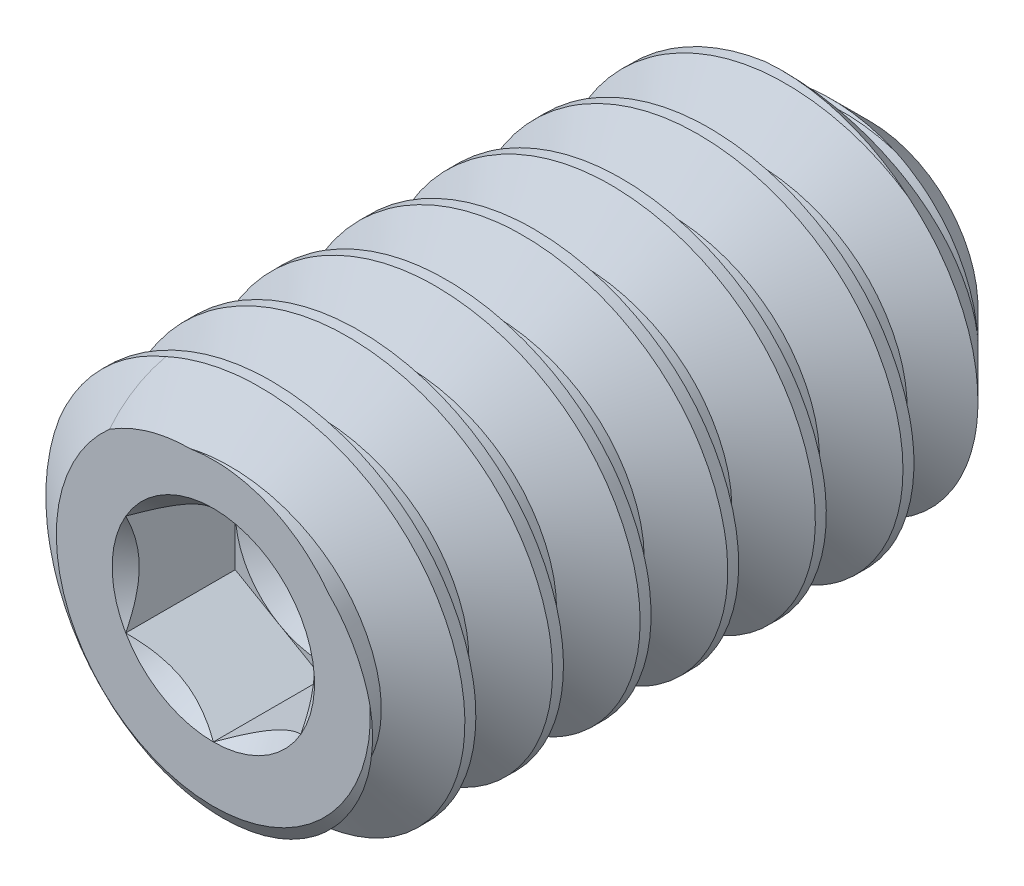
SolidWorks part; units mm, degrees
material "AISI 304"
ref_plane "Front" through (0, 0, 0) normal (0, 0, 1) x (1, 0, 0)
ref_plane "Top" through (0, 0, 0) normal (0, 1, 0) x (1, 0, 0)
ref_plane "Right" through (0, 0, 0) normal (1, 0, 0) x (0, 0, -1)
sketch "Sketch22" plane through (0, 0, 0) normal (1, 0, 0) x (0, 0, -1)
  line L0 (-2.1471, 0) -> (-2.1471, 1.1379)
  line L1 (-2.1471, 1.1379) -> (-1.9479, 1.4224)
  line L2 (-1.9479, 1.4224) -> (1.9724, 1.4224)
  line L3 (1.9724, 1.4224) -> (2.6154, 0.7794)
  line L4 (2.6154, 0.7794) -> (2.1471, 0)
  line L5 (2.1471, 0) -> (-2.1471, 0)
  line L6 (2.1471, 0) -> (2.6154, 0) construction
  line L7 (2.6154, 0) -> (2.6154, 0.7794) construction
  line L8 (2.6154, -0.7794) -> (2.1471, 0) construction
  line L9 (-1.9479, -1.4224) -> (1.9724, -1.4224) construction
  dimension "Dia" = 2.8448
  dimension "Length" = 4.7625
  dimension "D3" = 35
  dimension "D5" = 118
  dimension "D6" = 45
  dimension "D7" = 2.2758
revolve "Revolve1" add sketch "Sketch22" angle 360 about L6
ref_plane "Plane1" through (0, 0, -2.6154) normal (0, 0, 1) x (1, 0, 0)
sketch "Sketch27" plane through (0, 0, -2.6154) normal (0, 0, 1) x (1, 0, 0)
  circle A0 centre (0, 0) radius 1.4224 construction
  circle A1 centre (0, 0) radius 1.4224
curve "Helix/Spiral1" pitch 0.635 height 5.6515 radius 1.4224 centre (0, 0, -2.6154) axis (0, 0, 1) start towards (0, 1, 0)
sketch "Sketch28" plane through (0, 0, 0) normal (1, 0, 0) x (0, 0, -1)
  line L0 (2.6154, 1.4224) -> (3.171, 1.4224)
  line L1 (3.171, 1.4224) -> (2.9488, 1.0375)
  line L2 (2.9488, 1.0375) -> (2.8377, 1.0375)
  line L3 (2.8377, 1.0375) -> (2.6154, 1.4224)
  line L4 (2.7265, 1.2299) -> (3.0599, 1.2299) construction
  line L6 (-1.9479, 1.4224) -> (1.9724, 1.4224) construction
  line L7 (2.6154, 1.6137) -> (2.6154, -1.6137) construction
  dimension "D1" = 0.1111
  dimension "D3" = 60
  dimension "D2" = 0.5556
sweep "Cut-Sweep2" cut profiles "Sketch28" path "Helix/Spiral1" align with end faces yes
sketch "Sketch23" plane through (0, 0, 2.1471) normal (0, 0, 1) x (1, 0, 0)
  line L1 (0, 0.7332) -> (-0.635, 0.3666)
  line L2 (-0.635, 0.3666) -> (-0.635, -0.3666)
  line L3 (-0.635, -0.3666) -> (0, -0.7332)
  line L4 (0, -0.7332) -> (0.635, -0.3666)
  line L5 (0.635, -0.3666) -> (0.635, 0.3666)
  line L6 (0.635, 0.3666) -> (0, 0.7332)
  circle A0 centre (0, 0) radius 0.635 construction
  dimension "Hex" = 1.27
extrude "Cut-Extrude10" cut sketch "Sketch23" against normal blind 0.7937
sketch "Sketch24" plane through (0, 0, 2.1471) normal (0, 0, 1) x (1, 0, 0)
  circle A0 centre (0, 0) radius 0.7332
extrude "Cut-Extrude11" cut sketch "Sketch24" against normal through all draft 45
sketch "Sketch26" plane through (0, 0, 1.3533) normal (0, 0, 1) x (1, 0, 0)
  circle A0 centre (0, 0) radius 0.635 construction
  circle A1 centre (0, 0) radius 0.635
extrude "Cut-Extrude12" cut sketch "Sketch26" against normal through all draft 60
sketch "Sketch30" plane through (0, 0, 0) normal (1, 0, 0) x (0, 0, -1)
  line L0 (-1.9479, 1.4224) -> (1.9724, 1.4224) construction
  line L1 (-2.1471, 0) -> (-2.1471, 1.1379) construction
  line L2 (2.6154, 0) -> (2.6154, 0.7794) construction
  line L3 (-1.9479, -1.4224) -> (1.9724, -1.4224) construction
  point P0 (-2.1471, 1.4224)
  point P1 (2.6154, 1.4224)
  point P2 (2.6154, -1.4224)
  point P11 (1.0279, -1.4224)
  dimension "D1" = 1.5875
sketch "Sketch31" plane through (0, 0, 0) normal (1, 0, 0) x (0, 0, -1)
  line L2 (2.1471, 0) -> (2.6154, -0.7794)
  line L3 (2.6154, 0.7794) -> (2.1471, 0)
ref_plane "Plane2" through (0, 0, -2.6154) normal (0, 0, -1) x (-1, 0, 0)
ref_axis "Axis1" through (0, 0, -3.1643) along (0, 0, 1)
equation "\"D7@Sketch22\"=\"Dia@Sketch22\"*.8"
equation "\"D1@Sketch28\" = \"D4@Helix/Spiral1\" * .175"
equation "\"D3@Helix/Spiral1\" = \"Length@Sketch22\" + \"D4@Helix/Spiral1\" + .01"
equation "\"D1@Sketch30\" = \"D4@Helix/Spiral1\" * 2.5"
equation "\"hex Depth@Cut-Extrude10\" = \"Hex@Sketch23\" * .625"
equation "\"D2@Sketch28\" = \"D4@Helix/Spiral1\" * .875"
